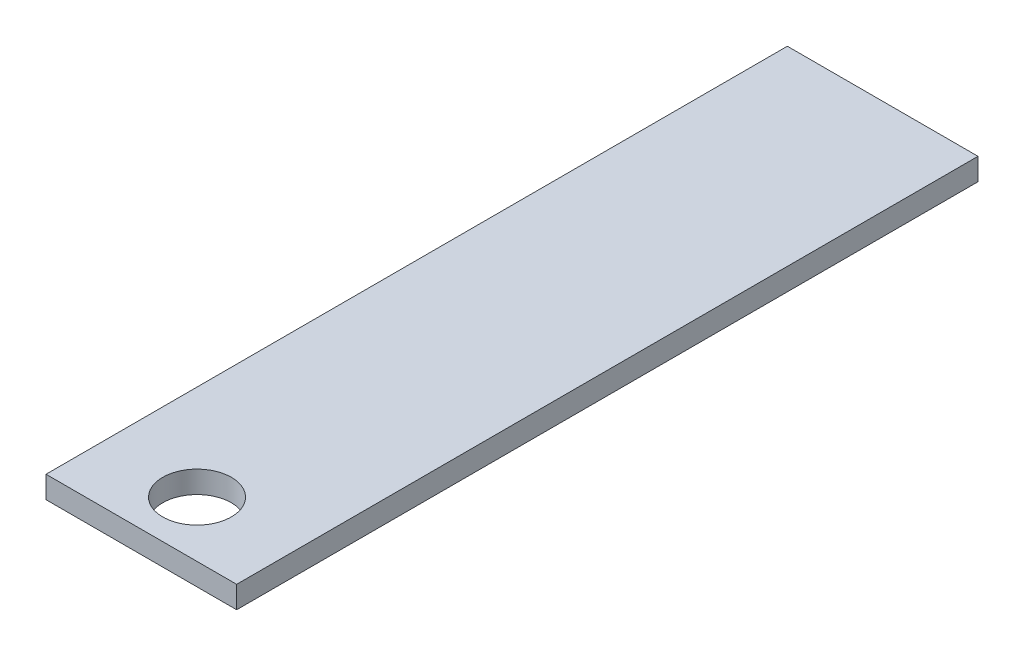
SolidWorks part; units mm, degrees
ref_plane "Front Plane" through (0, 0, 0) normal (0, 0, 1) x (1, 0, 0)
ref_plane "Top Plane" through (0, 0, 0) normal (0, 1, 0) x (1, 0, 0)
ref_plane "Right Plane" through (0, 0, 0) normal (1, 0, 0) x (0, 0, -1)
sketch "Sketch1" plane through (0, 0, 0) normal (0, 0, 1) x (1, 0, 0)
  line L7 (-30.861, -3.5719) -> (30.861, -3.5719)
  line L8 (-30.861, -3.5719) -> (-30.861, 3.5719)
  line L9 (-30.861, 3.5719) -> (30.861, 3.5719)
  line L10 (30.861, -3.5719) -> (30.861, 3.5719)
  line L11 (-30.861, -3.5719) -> (30.861, 3.5719) construction
  line L12 (-30.861, 3.5719) -> (30.861, -3.5719) construction
  point P4 (0, 0)
  point P14 (0, 0)
  dimension "Width" = 61.722
  dimension "Thickness" = 7.1437
sketch "Sketch2" plane through (0, 0, 0) normal (0, 1, 0) x (0, 0, -1)
  line L0 (120, 30.861) -> (-120, 30.861) construction
  point P0 (-42.8475, 30.861)
  point P4 (0, 30.861)
  point P6 (42.8475, 30.861)
  dimension "Length" = 240
  dimension "D1" = 77.1525
  dimension "D2" = 77.1525
sketch "Sketch3" plane through (0, 0, 0) normal (0, 0, 1) x (1, 0, 0)
  line L6 (-30.861, 3.5719) -> (30.861, 3.5719)
  line L7 (30.861, 3.5719) -> (30.861, -3.5719)
  line L8 (30.861, -3.5719) -> (-30.861, -3.5719)
  line L9 (-30.861, -3.5719) -> (-30.861, 3.5719)
extrude "Boss-Extrude1" add sketch "Sketch3" along normal mid plane 240
sketch "Sketch5" plane through (0, -3.5719, 0) normal (0, -1, 0) x (1, 0, 0)
  line L0 (0, 120) -> (0, 101.966) construction
  line L1 (-30.861, 120) -> (30.861, 120) construction
  circle A0 centre (0, 101.966) radius 11.1125
  dimension "D2" = 22.225
  dimension "D1" = 18.034
extrude "Cut-Extrude1" cut sketch "Sketch5" against normal up to next
equation "\"D1@Boss-Extrude1\" = \"Length@Sketch2\""
equation "\"D1@Sketch2\"=\"Width@Sketch1\" * 1.25"
equation "\"D2@Sketch2\"=\"D1@Sketch2\""
